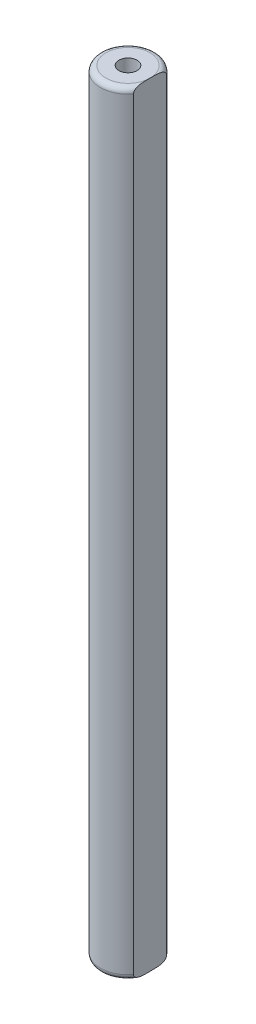
SolidWorks part; units mm, degrees
material "Alumina"
ref_plane "Front Plane" through (0, 0, 0) normal (0, 0, 1) x (1, 0, 0)
ref_plane "Top Plane" through (0, 0, 0) normal (0, 1, 0) x (1, 0, 0)
ref_plane "Right Plane" through (0, 0, 0) normal (1, 0, 0) x (0, 0, -1)
sketch "Sketch1" plane through (0, 0, 0) normal (0, 1, 0) x (1, 0, 0)
  circle A0 centre (0, 0) radius 2.5
  dimension "D1" = 5
extrude "Boss-Extrude1" add sketch "Sketch1" along normal blind 35.15
sketch "Sketch2" plane through (0, 35.15, 0) normal (0, 1, 0) x (1, 0, 0)
  circle A0 centre (0, 0) radius 0.825
  dimension "D1" = 1.65
extrude "Cut-Extrude1" cut sketch "Sketch2" against normal blind 5
sketch "Sketch3" plane through (0, 35.15, 0) normal (0, 1, 0) x (1, 0, 0)
  line L0 (2, 1.5) -> (2, -1.5)
  circle A0 centre (0, 0) radius 2.5 construction
  arc A1 (2, -1.5) -> (2, 1.5) centre (0, 0) ccw
  dimension "D1" = 3
extrude "Cut-Extrude2" cut sketch "Sketch3" against normal through all
fillet "Fillet1" radius 0.5 1 edges at (-2.5, 35.15, 0)
mirror "Mirror1" about plane through (0, 0, 0) normal (0, 1, 0) of "Fillet1", "Cut-Extrude2", "Cut-Extrude1", "Boss-Extrude1"
